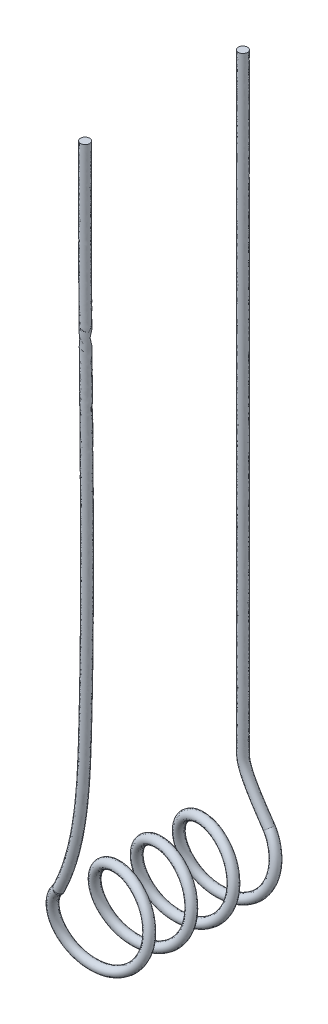
SolidWorks part; units mm, degrees
ref_plane "Front Plane" through (0, 0, 0) normal (0, 0, 1) x (1, 0, 0)
ref_plane "Top Plane" through (0, 0, 0) normal (0, 1, 0) x (1, 0, 0)
ref_plane "Right Plane" through (0, 0, 0) normal (1, 0, 0) x (0, 0, -1)
sketch "Sketch1" plane through (0, 0, 0) normal (0, 0, 1) x (1, 0, 0)
  circle A0 centre (0, 0) radius 0.8255
  dimension "D1" = 1.651
curve "Helix/Spiral1" pitch 0.9333 height 3.4999 radius 0.8255 left hand yes centre (0, 0, 0) axis (0, 0, 1) start towards (0.7071, 0.7071, 0)
ref_plane "Plane4" through (0, 0, 3.5) normal (0, 0, 1) x (1, 0, 0)
sketch "Sketch16" plane through (0, 0, 3.5) normal (0, 0, 1) x (1, 0, 0)
  line L0 (0, 0) -> (0, 7.8175) construction
  spline S0 degree 3 poles (-0.5859, 0.5855) (-0.0868, 1.6137) (0.1497, 6.6139) (-0.0311, 11.4508) (0, 15.24) knots 0 0 0 0 0.230363 1 1 1 1
  dimension "D1" = 15.24
sketch "Sketch17" plane through (0, 0, 0) normal (0, 0, 1) x (1, 0, 0)
  line L0 (0, 0) -> (0, 4.3257) construction
  spline S0 degree 3 poles (0.5837, 0.5837) (0.0409, 1.3649) (-0.0088, 1.6501) (0.0056, 2.1501) (-0.0034, 13.9216) (0, 15.24) knots 0 0 0 0 0.357027 0.532141 1 1 1 1
  dimension "D1" = 15.24
sweep "Sweep1" add path "Sketch17" circular profile diameter 0.2032 parameters "D3"=0.2032
sweep "Sweep2" add path "Helix/Spiral1" circular profile diameter 0.2032 parameters "D3"=0.2032
sweep "Sweep3" add path "Sketch16" circular profile diameter 0.2032 parameters "D3"=0.2032
